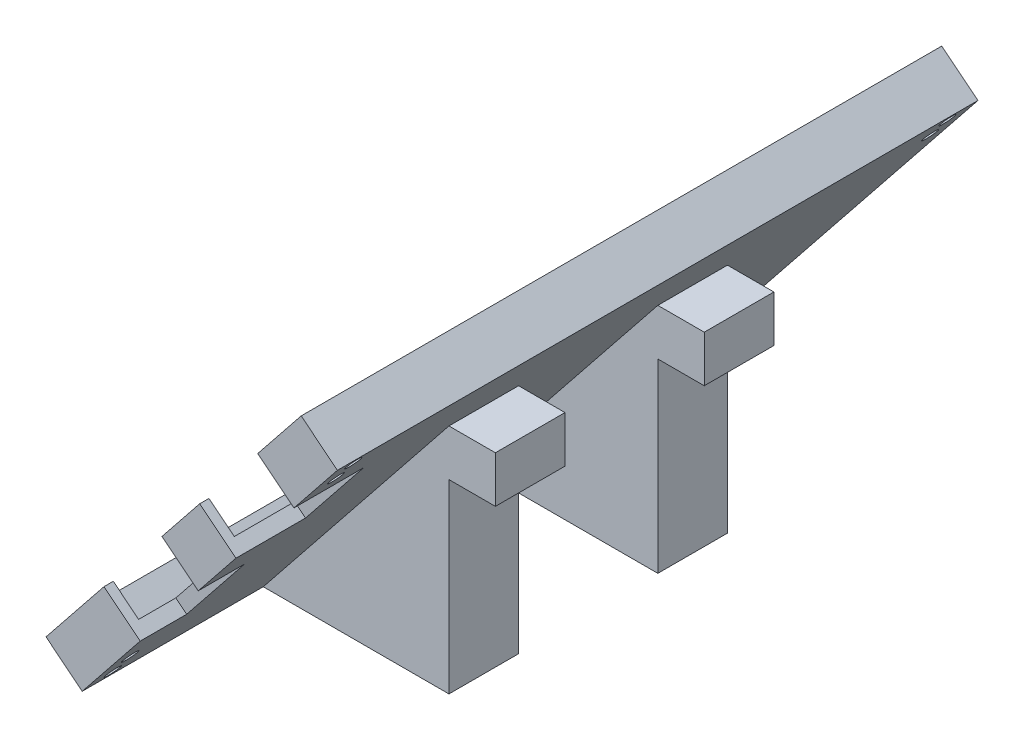
SolidWorks part; units mm, degrees
ref_plane "Alzado" through (0, 0, 0) normal (0, 0, 1) x (1, 0, 0)
ref_plane "Planta" through (0, 0, 0) normal (0, 1, 0) x (1, 0, 0)
ref_plane "Vista lateral" through (0, 0, 0) normal (1, 0, 0) x (0, 0, -1)
sketch "Croquis1" plane through (0, 0, 0) normal (0, 0, 1) x (1, 0, 0)
  line L0 (-20, 0) -> (20, 0)
  line L1 (20, 0) -> (20, 50)
  line L2 (20, 50) -> (-20, 0)
  dimension "D1" = 50
  dimension "D2" = 40
extrude "Saliente-Extruir1" add sketch "Croquis1" along normal blind 60
sketch "Croquis2" plane through (-12.1951, 9.7561, 0) normal (-0.7809, 0.6247, 0) x (0, 0, 1)
  line L0 (60, 51.5373) -> (0, 51.5373) construction
  line L1 (15, 51.5373) -> (45, 51.5373)
  line L2 (15, 51.5373) -> (15, -12.4939)
  line L3 (15, -12.4939) -> (45, -12.4939)
  line L4 (45, 51.5373) -> (45, -12.4939)
  line L5 (60, -12.4939) -> (0, -12.4939) construction
  line L6 (0, 51.5373) -> (0, -12.4939) construction
  line L7 (60, 51.5373) -> (60, -12.4939) construction
  dimension "D1" = 15
  dimension "D2" = 15
extrude "Cortar-Extruir1" cut sketch "Croquis2" against normal up to next
sketch "Croquis3" plane through (-12.1951, 9.7561, 0) normal (-0.7809, 0.6247, 0) x (0, 0, 1)
  line L0 (15, -12.4939) -> (0, -12.4939) construction
  line L1 (-39, 75.5061) -> (99, 75.5061)
  line L2 (-39, 75.5061) -> (-39, -12.4939)
  line L3 (-39, -12.4939) -> (99, -12.4939)
  line L4 (99, 75.5061) -> (99, -12.4939)
  line L7 (30, 75.5061) -> (30, -12.4939) construction
  line L8 (0, 51.5373) -> (0, -12.4939) construction
  point P12 (30, 75.5061)
  dimension "D1" = 138
  dimension "D2" = 88
  dimension "D3" = 30
extrude "Saliente-Extruir2" add sketch "Croquis3" along normal blind 3
sketch "Croquis4" plane through (20, 0, 0) normal (1, 0, 0) x (0, 0, -1)
  line L0 (-45, 0) -> (-45, 50) construction
  line L1 (-60, 50) -> (-45, 50)
  line L2 (-60, 50) -> (-60, 40)
  line L3 (-60, 40) -> (-45, 40)
  line L4 (-45, 50) -> (-45, 40)
  line L5 (0, 50) -> (0, 0) construction
  line L6 (-15, 50) -> (0, 50)
  line L7 (-15, 50) -> (-15, 40)
  line L8 (-15, 40) -> (0, 40)
  line L9 (0, 50) -> (0, 40)
  dimension "D1" = 10
  dimension "D2" = 10
extrude "Saliente-Extruir3" add sketch "Croquis4" along normal blind 10
sketch "Croquis5" plane through (-14.5377, 11.6302, 0) normal (-0.7809, 0.6247, 0) x (0, 0, 1)
  line L0 (99, -12.4939) -> (99, 75.5061) construction
  line L1 (-39, 75.5061) -> (99, 75.5061)
  line L2 (-39, 75.5061) -> (-39, 70.5061)
  line L3 (-39, 70.5061) -> (99, 70.5061)
  line L4 (99, 75.5061) -> (99, 70.5061)
  line L5 (-39, 75.5061) -> (-39, -12.4939) construction
  line L6 (-39, -7.4939) -> (99, -7.4939)
  line L7 (-39, -7.4939) -> (-39, -12.4939)
  line L8 (-39, -12.4939) -> (99, -12.4939)
  line L9 (99, -7.4939) -> (99, -12.4939)
  dimension "D1" = 5
  dimension "D2" = 5
extrude "Saliente-Extruir4" add sketch "Croquis5" along normal blind 7
sketch "Croquis6" plane through (-14.5377, 11.6302, 0) normal (-0.7809, 0.6247, 0) x (0, 0, 1)
  line L0 (-39, 67.0061) -> (99, 67.0061) construction
  line L1 (-39, 70.5061) -> (-39, -7.4939) construction
  line L2 (99, -7.4939) -> (99, 70.5061) construction
  line L3 (-39, -3.9939) -> (99, -3.9939) construction
  line L4 (-34, 70.5061) -> (-34, -7.4939) construction
  line L5 (-39, 70.5061) -> (99, 70.5061) construction
  line L6 (99, -7.4939) -> (-39, -7.4939) construction
  line L7 (94, 70.5061) -> (94, -7.4939) construction
  line L8 (-39, 70.5061) -> (99, 70.5061) construction
  line L9 (99, -7.4939) -> (-39, -7.4939) construction
  dimension "D1" = 5
  dimension "D2" = 5
  dimension "D3" = 3.5
  dimension "D4" = 3.5
hole_wizard "Taladro de margen para M31" positions "Croquis3D1" profile "Croquis7" hole size "M3" standard "ISO"
sketch3d "Croquis3D1"
  line L0 (27.3206, 63.9532, -39) -> (27.3206, 63.9532, 99) construction
  line L1 (29.5071, 66.6862, -34) -> (-19.2191, 5.7784, -34) construction
  line L2 (29.5071, 66.6862, 94) -> (-19.2191, 5.7784, 94) construction
  line L3 (-17.0327, 8.5115, -39) -> (-17.0327, 8.5115, 99) construction
  point P0 (27.3206, 63.9532, -34)
  point P6 (27.3206, 63.9532, 94)
  point P10 (-17.0327, 8.5115, 94)
  point P14 (-17.0327, 8.5115, -34)
sketch "Croquis7" plane through (27.3206, 63.9532, -34) normal (0, 0, 1) x (-0.6247, -0.7809, 0)
  line L0 (0, 0) -> (0, 5.9614)
  line L1 (0, 5.9614) -> (1.6, 5)
  line L2 (1.6, 5) -> (1.6, 0)
  line L5 (1.6, 0) -> (0, 0)
  line L10 (0, 5.9614) -> (-1.6, 5) construction
  line L11 (0, -6.35) -> (0, 107.95) construction
  dimension "Diámetro de taladro" = 3.2
  dimension "Profundidad de taladro" = 5
  dimension "Ángulo de perforador" = 118
sketch "Croquis9" plane through (-14.5377, 11.6302, 0) normal (-0.7809, 0.6247, 0) x (0, 0, 1)
  line L0 (99, -7.4939) -> (99, 70.5061) construction
  line L1 (99, 60.5061) -> (84, 60.5061)
  line L2 (99, 60.5061) -> (99, 40.5061)
  line L3 (99, 40.5061) -> (84, 40.5061)
  line L4 (84, 60.5061) -> (84, 40.5061)
  line L5 (-39, 70.5061) -> (99, 70.5061) construction
  line L6 (99, -7.4939) -> (-39, -7.4939) construction
  line L7 (89, 27.5061) -> (99, 27.5061)
  line L8 (89, 27.5061) -> (89, 7.5061)
  line L9 (89, 7.5061) -> (99, 7.5061)
  line L10 (99, 27.5061) -> (99, 7.5061)
  dimension "D1" = 10
  dimension "D2" = 20
  dimension "D3" = 15
  dimension "D4" = 15
  dimension "D5" = 20
  dimension "D6" = 10
extrude "Cortar-Extruir2" cut sketch "Croquis9" against normal up to next
sketch "Croquis10" plane through (-20.0038, 16.003, 0) normal (-0.7809, 0.6247, 0) x (0, 0, 1)
  line L0 (-39, 73.0061) -> (99, 73.0061) construction
  line L1 (-39, 75.5061) -> (-39, 70.5061) construction
  line L2 (99, 70.5061) -> (99, 75.5061) construction
  line L3 (-39, -9.9939) -> (99, -9.9939) construction
  line L4 (-39, -7.4939) -> (-39, -12.4939) construction
  line L5 (99, -12.4939) -> (99, -7.4939) construction
  line L6 (-34, 75.5061) -> (-34, -12.4939) construction
  line L7 (99, 75.5061) -> (-39, 75.5061) construction
  line L8 (-39, -12.4939) -> (99, -12.4939) construction
  line L9 (94, 75.5061) -> (94, -12.4939) construction
  dimension "D1" = 5
  dimension "D2" = 5
hole_wizard "Taladro de margen para M32" positions "Croquis3D2" profile "Croquis11" hole size "M3" standard "ISO" end condition up to next
sketch3d "Croquis3D2"
  line L0 (25.6027, 73.0112, -39) -> (25.6027, 73.0112, 99) construction
  line L1 (27.1645, 74.9634, -34) -> (-27.8087, 6.247, -34) construction
  line L2 (-26.247, 8.1991, -39) -> (-26.247, 8.1991, 99) construction
  line L3 (27.1645, 74.9634, 94) -> (-27.8087, 6.247, 94) construction
  point P0 (25.6027, 73.0112, -34)
  point P6 (-26.247, 8.1991, -34)
  point P10 (25.6027, 73.0112, 94)
  point P14 (-26.247, 8.1991, 94)
sketch "Croquis11" plane through (25.6027, 73.0112, -34) normal (0, 0, 1) x (-0.6247, -0.7809, 0)
  line L0 (0, 0) -> (0, 10)
  line L1 (0, 10) -> (1.6, 10)
  line L2 (1.6, 10) -> (1.6, 0)
  line L5 (1.6, 0) -> (0, 0)
  line L11 (0, -6.35) -> (0, 107.95) construction
  dimension "Diámetro de taladro hasta el siguiente" = 3.2
  dimension "Profundidad de taladro hasta el siguiente" = 10
sketch "Croquis12" plane through (-14.5377, 11.6302, 0) normal (-0.7809, 0.6247, 0) x (0, 0, 1)
  line L0 (99, -7.4939) -> (-39, -7.4939) construction
  line L1 (-39, 70.5061) -> (-37, 70.5061)
  line L2 (-39, 70.5061) -> (-39, -7.4939)
  line L3 (-39, -7.4939) -> (-37, -7.4939)
  line L4 (-37, 70.5061) -> (-37, -7.4939)
  line L5 (-39, 70.5061) -> (99, 70.5061) construction
  line L6 (99, 60.5061) -> (97, 60.5061)
  line L7 (99, 60.5061) -> (99, 70.5061)
  line L8 (99, 70.5061) -> (97, 70.5061)
  line L9 (97, 60.5061) -> (97, 70.5061)
  line L10 (99, 27.5061) -> (89, 27.5061) construction
  line L11 (99, 40.5061) -> (97, 40.5061)
  line L12 (99, 40.5061) -> (99, 27.5061)
  line L13 (99, 27.5061) -> (97, 27.5061)
  line L14 (97, 40.5061) -> (97, 27.5061)
  line L16 (99, 7.5061) -> (97, 7.5061)
  line L17 (99, 7.5061) -> (99, -7.4939)
  line L18 (99, -7.4939) -> (97, -7.4939)
  line L19 (97, 7.5061) -> (97, -7.4939)
  dimension "D1" = 2
  dimension "D2" = 2
  dimension "D3" = 2
  dimension "D4" = 2
extrude "Saliente-Extruir5" add sketch "Croquis12" along normal blind 7
